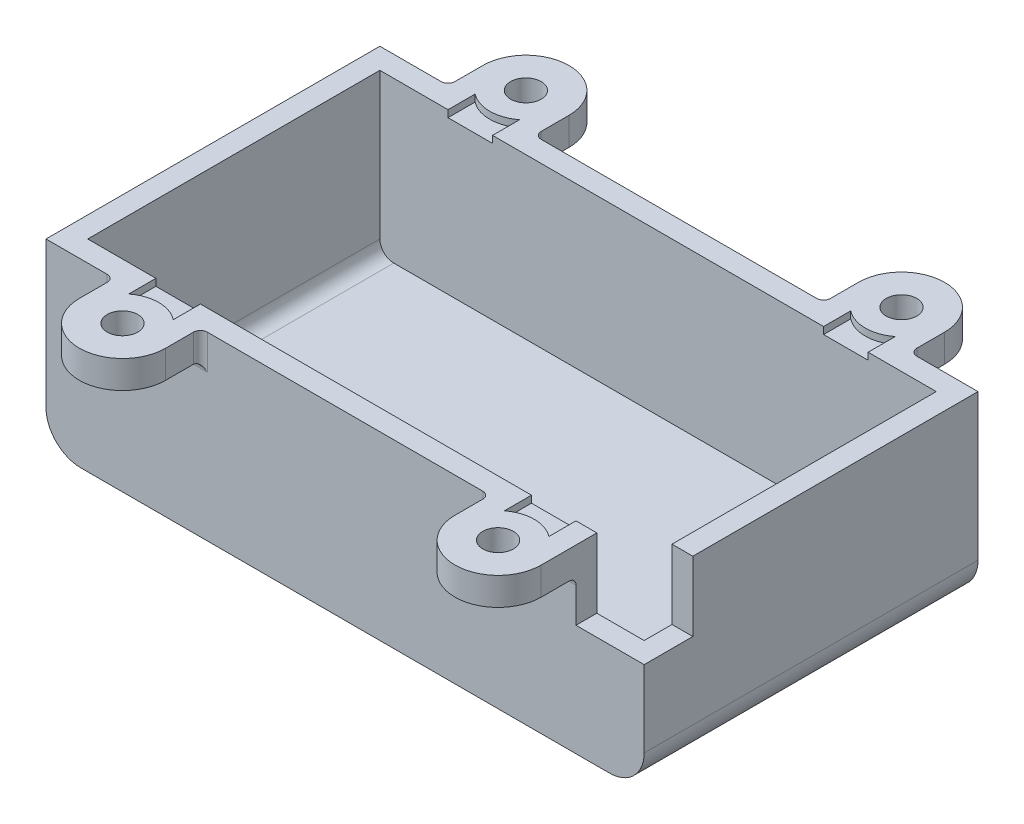
SolidWorks part; units mm, degrees
material "ABS"
ref_plane "Front Plane" through (0, 0, 0) normal (0, 0, 1) x (1, 0, 0)
ref_plane "Top Plane" through (0, 0, 0) normal (0, 1, 0) x (1, 0, 0)
ref_plane "Right Plane" through (0, 0, 0) normal (1, 0, 0) x (0, 0, -1)
sketch "Sketch1" plane through (0, 0, 0) normal (0, 0, 1) x (1, 0, 0)
  line L3 (-21.5, 13) -> (21.5, 13)
  line L4 (-21.5, 13) -> (-21.5, 2.5)
  line L5 (-19, 0) -> (19, 0)
  line L6 (21.5, 13) -> (21.5, 2.5)
  arc A0 (19, 0) -> (21.5, 2.5) centre (19, 2.5) ccw
  arc A1 (-21.5, 2.5) -> (-19, 0) centre (-19, 2.5) ccw
  point P6 (0, 0)
  dimension "D3" = 43
  dimension "D2" = 13
  dimension "D1" = 2.5
extrude "Boss-Extrude1" add sketch "Sketch1" along normal blind 24
sketch "Sketch3" plane through (0, 13, 0) normal (0, 1, 0) x (-1, 0, 0)
  line L0 (13.5, 26.5) -> (13.5, -2.5) construction
  line L1 (-21.5, 24) -> (21.5, 24) construction
  line L4 (-13.5, 26.5) -> (-13.5, -2.5) construction
  line L7 (0, 0) -> (0, 12) construction
  line L9 (-16.6, 24) -> (-16.6, -2.5)
  line L10 (-10.4, 24) -> (-16.6, 24)
  line L11 (-10.4, -2.5) -> (-10.4, 24)
  line L12 (-10.4, 0) -> (-16.6, 0)
  line L13 (-10.4, 26.5) -> (-10.4, 0)
  line L14 (10.4, -2.5) -> (10.4, 24)
  line L16 (10.4, 24) -> (16.6, 24)
  line L17 (16.6, 24) -> (16.6, -2.5)
  line L18 (10.4, 26.5) -> (10.4, 0)
  line L20 (10.4, 0) -> (16.6, 0)
  line L21 (16.6, 0) -> (16.6, 26.5)
  line L22 (-16.6, 0) -> (-16.6, 26.5)
  line L23 (-13.5, 12) -> (13.5, 12) construction
  circle A0 centre (-13.5, 26.5) radius 1.1
  circle A1 centre (-13.5, -2.5) radius 1.1
  circle A2 centre (13.5, 26.5) radius 1.1
  circle A3 centre (13.5, -2.5) radius 1.1
  arc A4 (-10.4, -2.5) -> (-16.6, -2.5) centre (-13.5, -2.5) cw
  arc A5 (-16.6, 26.5) -> (-10.4, 26.5) centre (-13.5, 26.5) cw
  arc A6 (10.4, -2.5) -> (16.6, -2.5) centre (13.5, -2.5) ccw
  arc A7 (16.6, 26.5) -> (10.4, 26.5) centre (13.5, 26.5) ccw
  line M41 (-21.5, 0) -> (21.5, 0)
  line M43 (21.5, 24) -> (-21.5, 24)
  dimension "D1" = 2.2
  dimension "D2" = 29
  dimension "D3" = 2
  dimension "D4" = 27
extrude "Boss-Extrude6" add sketch "Sketch3" against normal blind 2 contours L14 A6 L17 A3 M41 | A4 L11 L9 A1 M41 | A5 L22 L13 A0 M43 | L21 A7 L18 A2 M43 region at (16.5165, 13, 25.25) region at (13.5, 13, -0.0835) region at (-10.4835, 13, 25.25) region at (-13.5, 13, -0.0835)
shell "Shell1" thickness 1.5 removed face at (1.53, 13, 12)
sketch "Sketch5" plane through (0, 0, 0) normal (1, 0, 0) x (0, 0, -1)
  line L1 (-24, 13) -> (0, 13) construction
  line L2 (-24, 2.5) -> (-24, 13) construction
  line L3 (-24, 13) -> (-20.5, 13)
  line L4 (-24, 13) -> (-24, 8)
  line L5 (-24, 8) -> (-20.5, 8)
  line L6 (-20.5, 13) -> (-20.5, 8)
  dimension "D1" = 3.5
  dimension "D2" = 5
extrude "Cut-Extrude1" cut sketch "Sketch5" against normal up to surface (-16.6 mm away) from vertex up to face at (16.6, 11.75, 24.9375) starting at point (21.5, 13, 24)
fillet "Fillet1" radius 0.5 11 edges at (-10.4, 12, 24) (-16.6, 12, 24) (10.4, 12, 0) (16.6, 12, 0) (13.5, 11, 0) (-13.5, 11, 0) (13.5, 11, 24) (-13.5, 11, 24)
